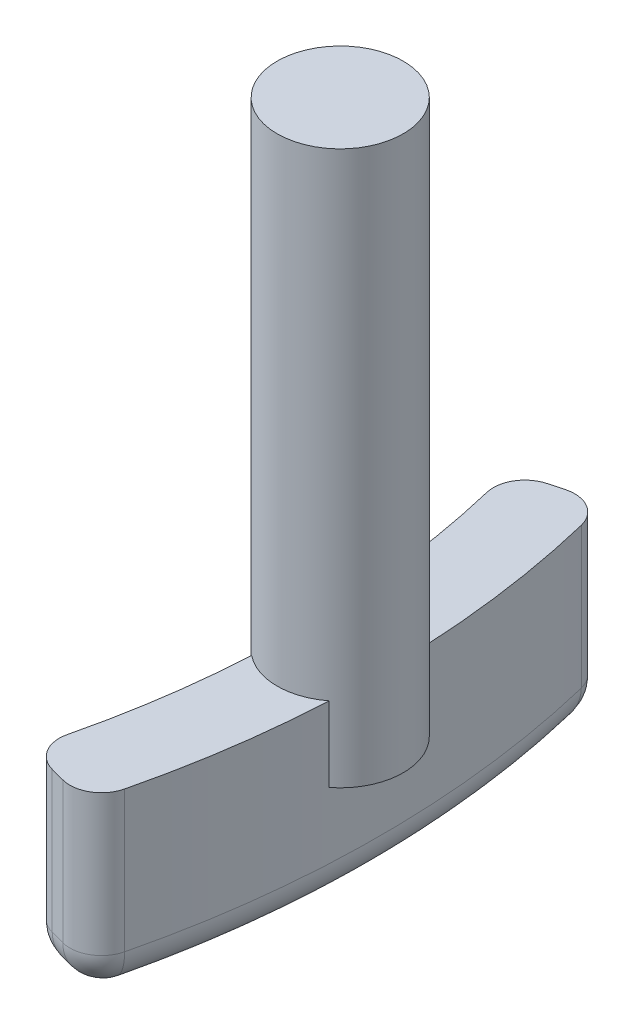
SolidWorks part; units mm, degrees
material "ABS"
ref_plane "Front Plane" through (0, 0, 0) normal (0, 0, 1) x (1, 0, 0)
ref_plane "Top Plane" through (0, 0, 0) normal (0, 1, 0) x (1, 0, 0)
ref_plane "Right Plane" through (0, 0, 0) normal (1, 0, 0) x (0, 0, -1)
sketch "Эскиз1" plane through (0, 0, 0) normal (0, 1, 0) x (1, 0, 0)
  line L12 (-0.9196, -8.2461) -> (-0.4365, -8.3755)
  line L13 (-0.9196, 8.2461) -> (-0.4365, 8.3755)
  arc A36 (-0.4365, -8.3755) -> (0.8557, -7.6087) centre (-0.1648, -7.3613) ccw
  arc A37 (0.8557, 7.6087) -> (0.8557, -7.6087) centre (-30.5354, 0) cw
  arc A38 (0.8557, 7.6087) -> (-0.4365, 8.3755) centre (-0.1648, 7.3613) ccw
  arc A39 (-0.9196, 8.2461) -> (-1.6684, 6.9849) centre (-0.6479, 7.2319) ccw
  arc A40 (-1.6684, 6.9849) -> (-1.6684, -6.9849) centre (-30.5354, 0) cw
  arc A41 (-0.9196, -8.2461) -> (-1.6684, -6.9849) centre (-0.6479, -7.2319) cw
  point P14 (0.3409, -8.2822)
extrude "Бобышка-Вытянуть1" add sketch "Эскиз1" along normal blind 5
ref_plane "Плоскость1" through (0, 2.5, 0) normal (0, 1, 0) x (1, 0, 0)
sketch "Эскиз2" plane through (0, 2.5, 0) normal (0, 1, 0) x (1, 0, 0)
  circle A2 centre (0.4313, 0) radius 2.1
  dimension "D1" = 4.2
extrude "Бобышка-Вытянуть2" add sketch "Эскиз2" along normal blind 18.44
sketch "Эскиз3" plane through (0, 0, 0) normal (0, -1, 0) x (1, 0, 0)
  line L6 (-0.4365, -8.3755) -> (-0.9196, -8.2461)
  line L7 (-0.9196, 8.2461) -> (-0.4365, 8.3755)
  arc A18 (-1.6684, -6.9849) -> (-0.9196, -8.2461) centre (-0.6479, -7.2319) ccw
  arc A19 (-1.6684, -6.9849) -> (-1.6684, 6.9849) centre (-30.5354, 0) ccw
  arc A20 (-0.9196, 8.2461) -> (-1.6684, 6.9849) centre (-0.6479, 7.2319) ccw
  arc A21 (0.8557, 7.6087) -> (-0.4365, 8.3755) centre (-0.1648, 7.3613) ccw
  arc A22 (0.8557, -7.6087) -> (0.8557, 7.6087) centre (-30.5354, 0) ccw
  arc A23 (-0.4365, -8.3755) -> (0.8557, -7.6087) centre (-0.1648, -7.3613) ccw
extrude "Бобышка-Вытянуть3" add sketch "Эскиз3" along normal blind 1
fillet "Скругление2" radius 1.3 8 edges at (-0.6781, -1, -8.3108) (-1.5507, -1, -7.7679) (-0.8354, -1, 0) (-1.5507, -1, 7.7679) (-0.6781, -1, 8.3108) (0.3711, -1, 8.2643) (1.7646, -1, 0) (0.3711, -1, -8.2643)
